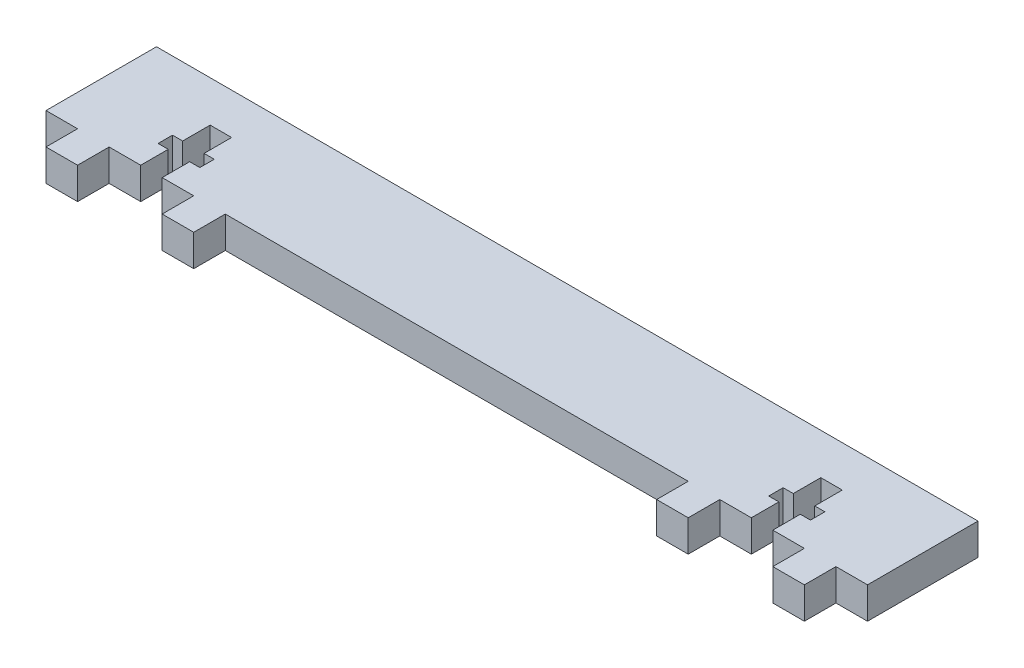
SolidWorks part; units mm, degrees
ref_plane "Front Plane" through (0, 0, 0) normal (0, 0, 1) x (1, 0, 0)
ref_plane "Top Plane" through (0, 0, 0) normal (0, 1, 0) x (1, 0, 0)
ref_plane "Right Plane" through (0, 0, 0) normal (1, 0, 0) x (0, 0, -1)
sketch "Sketch1" plane through (0, 0, 0) normal (0, 1, 0) x (1, 0, 0)
  line L0 (0, 11.1125) -> (0, -11.1125) construction
  line L1 (-82.6262, -11.1125) -> (-76.2762, -11.1125)
  line L2 (-82.6262, -11.1125) -> (-82.6262, 11.1125)
  line L3 (-82.6262, 11.1125) -> (82.6262, 11.1125)
  line L4 (82.6262, -11.1125) -> (82.6262, 11.1125)
  line L5 (-82.6262, -11.1125) -> (82.6262, 11.1125) construction
  line L6 (-82.6262, 11.1125) -> (82.6262, -11.1125) construction
  line L7 (-46.5582, -11.1125) -> (46.5582, -11.1125)
  line L8 (82.6262, -11.1125) -> (76.2762, -11.1125)
  point P0 (0, 0)
  line B0 (-69.9262, -11.1125) -> (-69.9262, -17.4625)
  line B1 (-69.9262, -17.4625) -> (-76.2762, -17.4625)
  line B2 (-76.2762, -17.4625) -> (-76.2762, -11.1125)
  line B3 (-63.5762, -11.1125) -> (-63.5762, -5.5775)
  line B4 (-63.5762, -5.5775) -> (-65.6172, -5.5775)
  line B5 (-65.6172, -5.5775) -> (-65.6172, -2.6775)
  line B6 (-65.6172, -2.6775) -> (-63.5762, -2.6775)
  line B7 (-63.5762, -2.6775) -> (-63.5762, 2.8575)
  line B8 (-63.5762, 2.8575) -> (-59.2582, 2.8575)
  line B9 (-59.2582, 2.8575) -> (-59.2582, -2.6775)
  line B10 (-59.2582, -2.6775) -> (-57.2172, -2.6775)
  line B11 (-57.2172, -2.6775) -> (-57.2172, -5.5775)
  line B12 (-57.2172, -5.5775) -> (-59.2582, -5.5775)
  line B13 (-59.2582, -5.5775) -> (-59.2582, -11.1125)
  line B14 (-61.4172, 2.8575) -> (-61.4172, -11.1125) construction
  line B15 (-52.9082, -11.1125) -> (-59.2582, -11.1125)
  line B16 (-46.5582, -17.4625) -> (-46.5582, -11.1125)
  line B17 (-69.9262, -11.1125) -> (-63.5762, -11.1125)
  line B18 (-52.9082, -17.4625) -> (-46.5582, -17.4625)
  line B19 (-52.9082, -11.1125) -> (-52.9082, -17.4625)
  line B20 (69.9262, -11.1125) -> (69.9262, -17.4625)
  line B21 (69.9262, -17.4625) -> (76.2762, -17.4625)
  line B22 (76.2762, -17.4625) -> (76.2762, -11.1125)
  line B23 (63.5762, -11.1125) -> (63.5762, -5.5775)
  line B24 (63.5762, -5.5775) -> (65.6172, -5.5775)
  line B25 (65.6172, -5.5775) -> (65.6172, -2.6775)
  line B26 (65.6172, -2.6775) -> (63.5762, -2.6775)
  line B27 (63.5762, -2.6775) -> (63.5762, 2.8575)
  line B28 (63.5762, 2.8575) -> (59.2582, 2.8575)
  line B29 (59.2582, 2.8575) -> (59.2582, -2.6775)
  line B30 (59.2582, -2.6775) -> (57.2172, -2.6775)
  line B31 (57.2172, -2.6775) -> (57.2172, -5.5775)
  line B32 (57.2172, -5.5775) -> (59.2582, -5.5775)
  line B33 (59.2582, -5.5775) -> (59.2582, -11.1125)
  line B34 (61.4172, 2.8575) -> (61.4172, -11.1125) construction
  line B35 (52.9082, -11.1125) -> (59.2582, -11.1125)
  line B36 (46.5582, -17.4625) -> (46.5582, -11.1125)
  line B37 (69.9262, -11.1125) -> (63.5762, -11.1125)
  line B38 (52.9082, -17.4625) -> (46.5582, -17.4625)
  line B39 (52.9082, -11.1125) -> (52.9082, -17.4625)
  dimension "D1" = 22.225
  dimension "D2" = 93.1164
  dimension "D3" = 6.35
sketch_block_instance "Male T-slot assembly-1"
sketch_block "Male T-slot assembly" parameters "D1"=6.35, "D2"=6.35, "D3"=4.318, "D4"=2.9, "D5"=8.4, "D6"=13.97, "D7"=6.35
sketch_block_instance "Male T-slot assembly-3"
extrude "Boss-Extrude1" add sketch "Sketch1" along normal blind 6.35 contours B39 B35 B33 B32 B31 B30 B29 B28 B27 B26 B25 B24 B23 B37 B20 B21 B22 L8 L4 L3 L2 L1 B2 B1 B0 B17 B3 B4 B5 B6 B7 B8 B9 B10 B11 B12 B13 B15 B19 B18 B16 L7 B36 B38 region at (0, 0, 0.4631)
equation "\"Ball Diameter\"= 1.75in"
equation "\"Ball Radius\" = \"Ball Diameter\"/2"
equation "\"Sheet Thickness\"= 0.25in"
equation "\"Screw Diameter\"= .17in"
equation "\"Robot Diameter\"= 14in"
equation "\"Castor Screw Diameter\"= 0.22in"
equation "\"Wheel Diameter\" = 4in"
equation "\"Nut Diameter\" = 8.4mm"
equation "\"Nut Height\" = 2.9mm"
equation "\"Screw Height\" = 0.55in"
equation "\"Pulley Diameter\" = 1in"
equation "\"Reactor Height\" = 14in"
equation "\"Elevator Height\" = 11.5in"
equation "\"Elevator Width\" = \"Ball Diameter\" + 0.25in"
equation "\"Elevator Bearing Diameter\" = sqr(2*(\"Sheet Thickness\"^2)) + 0.2in"
equation "\"Elevator Axle Endcap Diameter\" = \"Pulley Diameter\" + 0.25in"
equation "\"Elevator Axle Length\" = \"Elevator Width\" + 8*\"Sheet Thickness\""
equation "\"Elevator Clearance from Axis\" = 3.28in"
equation "\"Elevator Horizontal Clearance\" = \"Elevator Width\" + 0.5in"
equation "\"Claw Horizontal Seperation\" = (\"Elevator Width\"/2) - (1.5 * \"Sheet Thickness\") - 0.15in"
equation "\"Claw Radius\" = \"Ball Radius\" + 0.1in"
equation "\"Castor Wheel Height\" = 1.25in"
equation "\"Length of Chute\" = 8in"
equation "\"D1@Sketch1\"=\"Ball Radius\""
